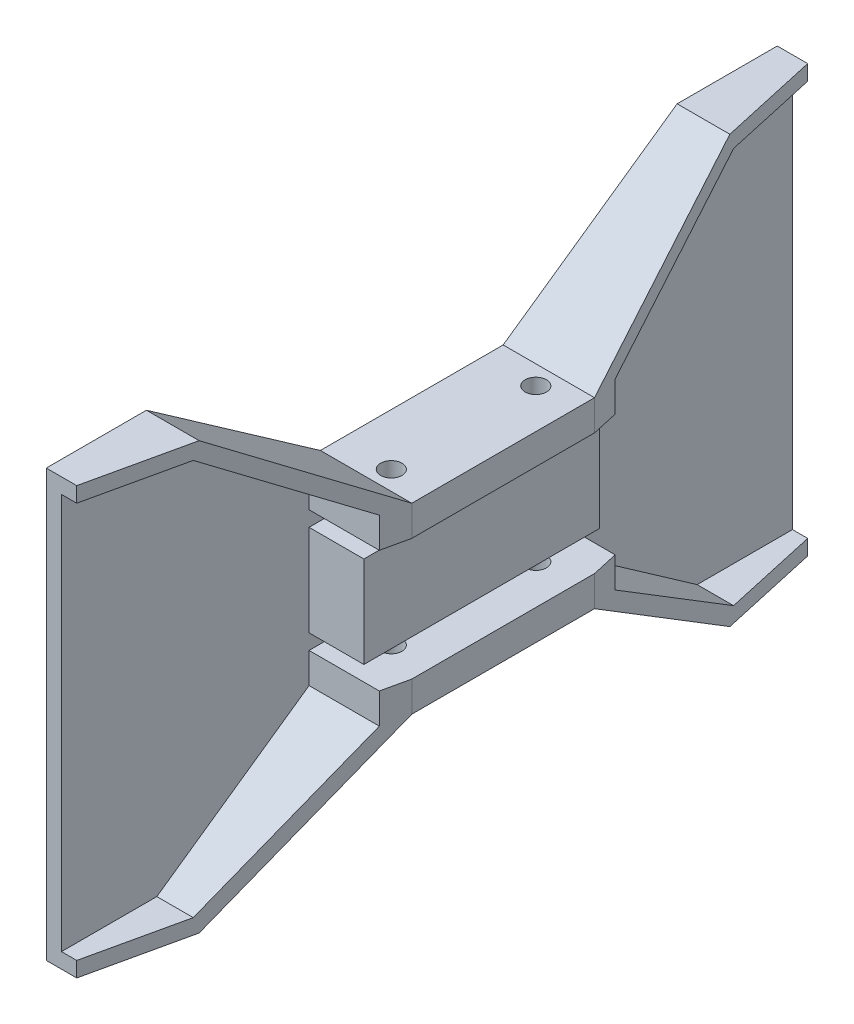
SolidWorks part; units mm, degrees
ref_plane "Front Plane" through (0, 0, 0) normal (1, 0, 0) x (0, 1, 0)
ref_plane "Top Plane" through (0, 0, 0) normal (0, 0, 1) x (0, 1, 0)
ref_plane "Right Plane" through (0, 0, 0) normal (0, 1, 0) x (-1, 0, 0)
sketch "Sketch1" plane through (0, 0, 0) normal (1, 0, 0) x (0, 1, 0)
  line L0 (-38.1, 0) -> (-38.1, -38.1)
  line L1 (0, 0) -> (-88.9, 0)
  line L2 (0, 0) -> (0, -152.4)
  line L3 (0, -152.4) -> (-88.9, -152.4)
  line L4 (-88.9, 0) -> (-88.9, -152.4)
  line L5 (-38.1, -38.1) -> (-88.9, -110.6499)
  line L6 (-82.55, -152.4) -> (-82.55, -112.6521)
  line L7 (-82.55, -112.6521) -> (-38.1, -49.1709)
  line L8 (-38.1, -49.1709) -> (-25.4, -49.1709)
  line L9 (-25.4, -49.1709) -> (-25.4, 0)
  line L10 (-19.05, 0) -> (-19.05, -49.1709)
  line L11 (-19.05, -49.1709) -> (0, -49.1709)
  dimension "D1" = 88.9
  dimension "D2" = 152.4
  dimension "D3" = 38.1
  dimension "D4" = 35
  dimension "D5" = 114.3
  dimension "D6" = 6.35
  dimension "D7" = 6.35
  dimension "D8" = 12.7
  dimension "D9" = 6.35
extrude "Boss-Extrude1" add sketch "Sketch1" against normal blind 6.35 contours L11 L10 L1 L9 L8 L7 L6 L3 L2 | L8 L9 L1 L0 L5 L4 L3 L6 L7 | L10 L11 L2 L1 region at (0, -52.9449, -64.1013) region at (0, -35.4448, -103.3686) region at (0, -9.525, -24.5854)
extrude "Boss-Extrude2" add sketch "Sketch1<4>" along normal blind 38.1 from surface contours L8 L9 L1 L0 L5 L4 L3 L6 L7 | L10 L11 L2 L1 region at (0, -52.9449, -64.1013) region at (0, -9.525, -24.5854) starting at face at (-6.35, -42.3333, -75.5917)
sketch "Sketch1<4>" plane through (0, 0, 0) normal (1, 0, 0) x (0, 1, 0) same geometry as "Sketch1"
extrude "Cut-Extrude1" cut sketch "Sketch1<6>" against normal blind 8.89 from surface contours L10 L11 L2 L1 region at (0, -9.525, -24.5854) starting at face at (31.75, -9.525, -24.5854)
sketch "Sketch1<6>" plane through (0, 0, 0) normal (1, 0, 0) x (0, 1, 0) same geometry as "Sketch1"
sketch "Sketch3" plane through (0, 0, 0) normal (0, 1, 0) x (-1, 0, 0)
  line L0 (-31.75, -49.1709) -> (0, -49.1709) construction
  line L1 (0, -112.6521) -> (0, -152.4) construction
  line L2 (0, -49.1709) -> (0, -112.6521) construction
  line L3 (-31.75, -152.4) -> (0, -152.4) construction
  line L4 (-31.75, -112.6521) -> (0, -112.6521) construction
  line L5 (-31.75, -152.4) -> (-31.75, -112.6521) construction
  line L6 (-31.75, -112.6521) -> (-31.75, -49.1709) construction
  line L7 (-31.75, -49.1709) -> (0, -49.1709)
  line L8 (0, -112.6521) -> (0, -152.4)
  line L9 (0, -49.1709) -> (0, -112.6521)
  line L10 (-31.75, -152.4) -> (0, -152.4)
  line L11 (-31.75, -112.6521) -> (0, -112.6521)
  line L12 (-31.75, -152.4) -> (-31.75, -112.6521)
  line L13 (-31.75, -112.6521) -> (-31.75, -49.1709)
  line L14 (6.35, -38.1) -> (-31.75, -38.1) construction
  line L15 (6.35, 0) -> (6.35, -152.4) construction
  line L16 (6.35, -38.1) -> (-31.75, -38.1)
  line L17 (-31.75, -38.1) -> (-31.75, -49.1709)
  line L18 (-31.75, -38.1) -> (-6.35, -152.4)
  circle A0 centre (-15.24, -30.1209) radius 4.445
  dimension "D2" = 8.89
  dimension "D1" = 12.7
  dimension "D3" = 19.05
  dimension "D4" = 21.59
extrude "Cut-Extrude2" cut sketch "Sketch3" against normal through all contours L13 L11 | L11 L12 L10 | A0 | L18 L17 L7 region at (30.9299, 0, -45.4806) region at (26.1216, 0, -88.7557) region at (21.1033, 0, -133.9203) region at (15.24, 0, -30.1209)
mirror "Mirror1" about plane through (-6.35, 0, 0) normal (0, -1, 0) of bodies 104
mirror "Mirror2" about plane through (-6.35, 0, 0) normal (0, 0, 1) of bodies 105
